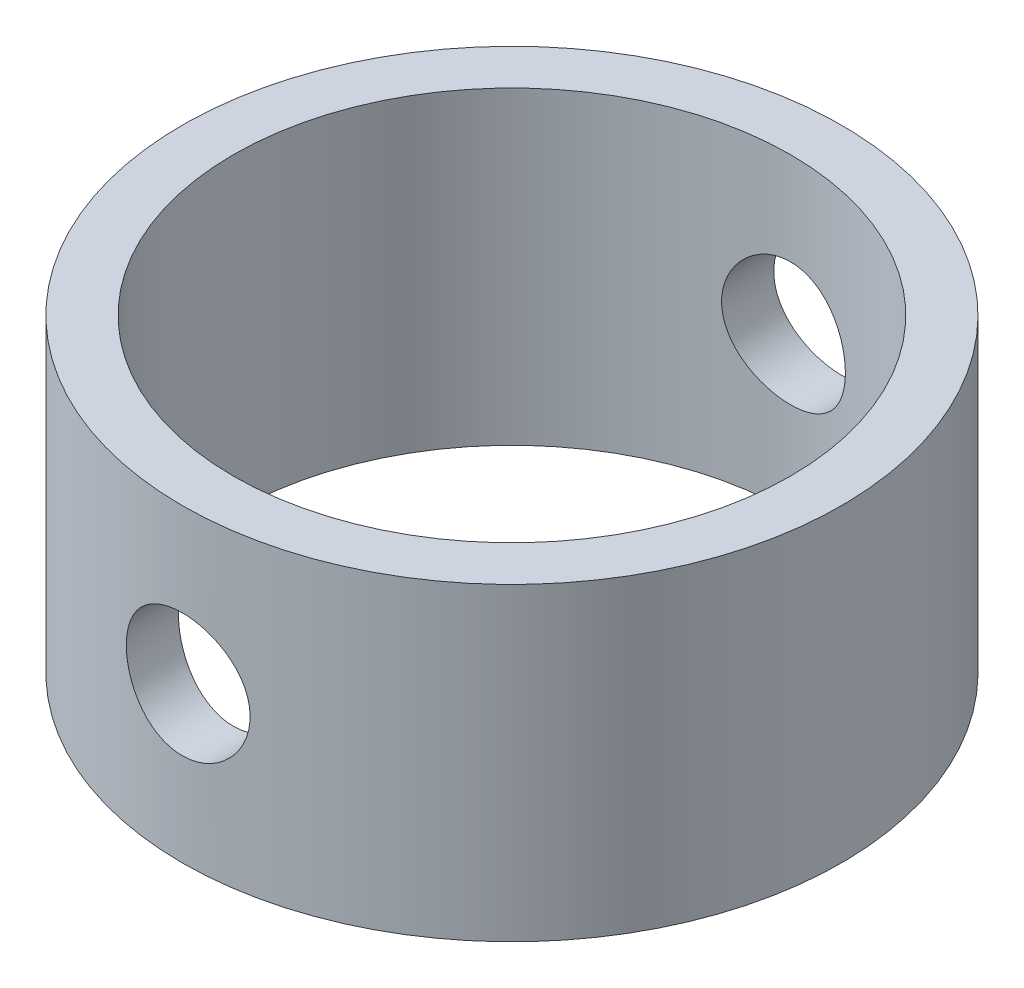
SolidWorks part; units mm, degrees
ref_plane "Front Plane" through (0, 0, 0) normal (0, 0, 1) x (1, 0, 0)
ref_plane "Top Plane" through (0, 0, 0) normal (0, 1, 0) x (1, 0, 0)
ref_plane "Right Plane" through (0, 0, 0) normal (1, 0, 0) x (0, 0, -1)
sketch "Sketch1" plane through (0, 0, 0) normal (0, 1, 0) x (1, 0, 0)
  circle A0 centre (0, 0) radius 27.051
  circle A1 centre (0, 0) radius 22.86
  dimension "D1" = 54.102
  dimension "D2" = 45.72
extrude "Boss-Extrude1" add sketch "Sketch1" along normal blind 12.7 and the other way blind 12.7
sketch "Sketch2" plane through (0, 0, 0) normal (0, 0, 1) x (1, 0, 0)
  circle A0 centre (0, 0) radius 5.08
  dimension "D1" = 10.16
extrude "Cut-Extrude1" cut sketch "Sketch2" against normal up to next and the other way up to next
